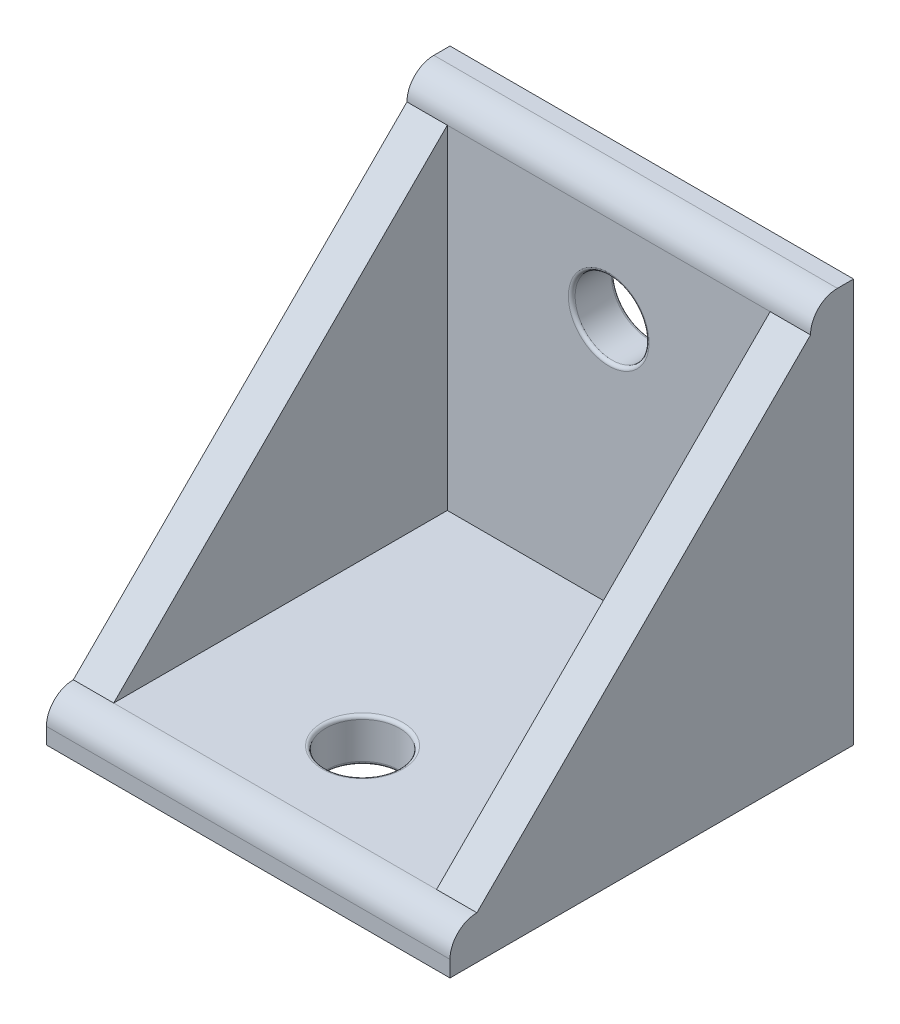
SolidWorks part; units mm, degrees
ref_plane "Front Plane" through (0, 0, 0) normal (0, 0, 1) x (1, 0, 0)
ref_plane "Top Plane" through (0, 0, 0) normal (0, 1, 0) x (1, 0, 0)
ref_plane "Right Plane" through (0, 0, 0) normal (1, 0, 0) x (0, 0, -1)
sketch "Sketch1" plane through (0, 0, 0) normal (0, 1, 0) x (1, 0, 0)
  line L1 (-15, -15) -> (15, -15)
  line L2 (-15, -15) -> (-15, 15)
  line L3 (-15, 15) -> (15, 15)
  line L4 (15, -15) -> (15, 15)
  line L5 (-15, -15) -> (15, 15) construction
  line L6 (-15, 15) -> (15, -15) construction
  point P0 (0, 0)
  dimension "D1" = 30
  dimension "D2" = 30
extrude "Boss-Extrude1" add sketch "Sketch1" along normal blind 3.2
sketch "Sketch2" plane through (0, 3.2, 0) normal (0, 1, 0) x (1, 0, 0)
  line L0 (15, -15) -> (15, 15) construction
  line L1 (-15, 15) -> (15, 15)
  line L2 (-15, 15) -> (-15, 11.8)
  line L3 (-15, 11.8) -> (15, 11.8)
  line L4 (15, 15) -> (15, 11.8)
  dimension "D1" = 3.2
extrude "Boss-Extrude2" add sketch "Sketch2" along normal blind 26.8
sketch "Sketch3" plane through (0, 3.2, 0) normal (0, 1, 0) x (1, 0, 0)
  line L0 (-15, -15) -> (15, -15) construction
  circle A0 centre (0, -6.5) radius 2.75
  point P3 (0, 0)
  point P4 (0, 0)
  point P5 (0, -9.127)
  point P8 (0, 0)
  dimension "D1" = 5.5
  dimension "D2" = 8.5
extrude "Cut-Extrude1" cut sketch "Sketch3" against normal through all
sketch "Sketch4" plane through (0, 0, -11.8) normal (0, 0, 1) x (1, 0, 0)
  line L0 (-15, 30) -> (15, 30) construction
  circle A0 centre (0, 21.5) radius 2.75
  point P2 (0, 0)
  dimension "D2" = 5.5
  dimension "D1" = 8.5
extrude "Cut-Extrude2" cut sketch "Sketch4" against normal through all
fillet "Fillet1" radius 2 2 edges at (0, 30, -11.8) (0, 3.2, 15)
fillet "Fillet2" radius 0.25 4 edges at (2.75, 21.5, -11.8) (2.75, 21.5, -15) (0, 3.2, 9.25) (0, 0, 9.25)
sketch "Sketch7" plane through (15, 0, 0) normal (1, 0, 0) x (0, 0, -1)
  line L0 (11.8, 3.2) -> (11.8, 28)
  line L1 (11.8, 28) -> (11.8, 3.2) construction
  line L2 (11.8, 28) -> (-13, 3.2)
  line L3 (-13, 3.2) -> (11.8, 3.2) construction
  line L4 (-13, 3.2) -> (11.8, 3.2)
  point P5 (11.8, 13.2253)
  point P9 (0, 0)
  point P10 (11.8, 28)
  point P11 (11.8, 23.8735)
extrude "Boss-Extrude3" add sketch "Sketch7" against normal blind 3
mirror "Mirror1" about plane through (0, 0, 0) normal (1, 0, 0) of "Boss-Extrude3"
